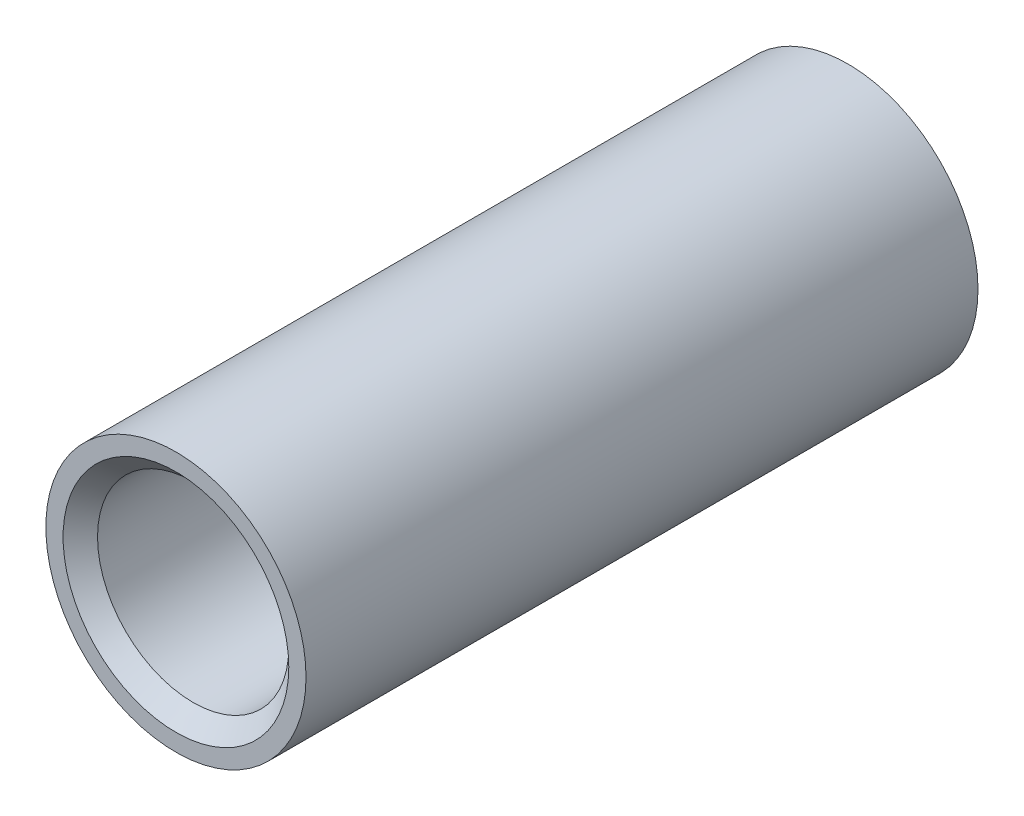
SolidWorks part; units mm, degrees
ref_plane "前视基准面" through (0, 0, 0) normal (0, 0, 1) x (1, 0, 0)
ref_plane "上视基准面" through (0, 0, 0) normal (0, 1, 0) x (1, 0, 0)
ref_plane "右视基准面" through (0, 0, 0) normal (1, 0, 0) x (0, 0, -1)
sketch "草图1" plane through (0, 0, 0) normal (0, 0, 1) x (1, 0, 0)
  circle A0 centre (0, 0) radius 15.1
  dimension "D1" = 30.2
extrude "凸台-拉伸1" add sketch "草图1" along normal blind 39 contours A0
ref_plane "基准面1" through (0, 0, 37.25) normal (0, 0, 1) x (1, 0, 0)
sketch "草图4" plane through (0, 0, 39) normal (0, 0, 1) x (1, 0, 0)
  circle A0 centre (0, 0) radius 11.1
  circle A1 centre (0, 0) radius 15.1 construction
  dimension "D1" = 4
extrude "中孔" cut sketch "草图4" against normal through all contours A0
sketch "草图8" plane through (0, 0, 0) normal (0, 1, 0) x (1, 0, 0)
  line L0 (-11.1, 0) -> (-11.1, -39) construction
  line L1 (-11.1, -37) -> (-11.1, -39)
  line L4 (-11.1, -37) -> (-13.1, -39)
  line L5 (-15.1, -39) -> (15.1, -39) construction
  line L6 (-13.1, -39) -> (-11.1, -39)
  line L7 (0, 0) -> (0, 50000) construction
  dimension "D1" = 2
  dimension "D2" = 2
revolve "切除-旋转1" cut sketch "草图8" angle 360 about L7
ref_plane "基准面3" through (0, 0, 35.25) normal (0, 0, 1) x (1, 0, 0)
extrude "凸台-拉伸3" add sketch "草图1<6>" against normal blind 39
sketch "草图1<6>" plane through (0, 0, 0) normal (0, 0, 1) x (1, 0, 0) same geometry as "草图1"
sketch "草图12" plane through (0, 0, 0) normal (0, 0, 1) x (1, 0, 0)
  circle A0 centre (0, 0) radius 11
  circle A1 centre (0, 0) radius 15.1 construction
extrude "切除-拉伸2" cut sketch "草图12" against normal blind 80
ref_plane "基准面4" through (0, 0, -39) normal (0, 0, -1) x (-1, 0, 0)
ref_plane "基准面5" through (0, 0, -35.25) normal (0, 0, -1) x (-1, 0, 0)
sketch "草图13" plane through (0, 0, -35.25) normal (0, 0, -1) x (-1, 0, 0)
  circle A0 centre (0, 0) radius 11
  circle A1 centre (0, 0) radius 15.1 construction
  point P5 (0, 0)
  point P6 (0, 0)
sketch "草图14" plane through (0, 0, 0) normal (0, 1, 0) x (1, 0, 0)
  line L0 (11, 39) -> (13, 39)
  line L1 (13, 39) -> (11, 37)
  line L2 (11, 37) -> (11, 39)
  line L4 (0, 39) -> (0, 30.5258) construction
  point P7 (0, 0)
  point P8 (0, 30.5258)
  point P9 (0, 0)
  dimension "D1" = 2
  dimension "D2" = 2
revolve "切除-旋转2" cut sketch "草图14" angle 360 about L4
